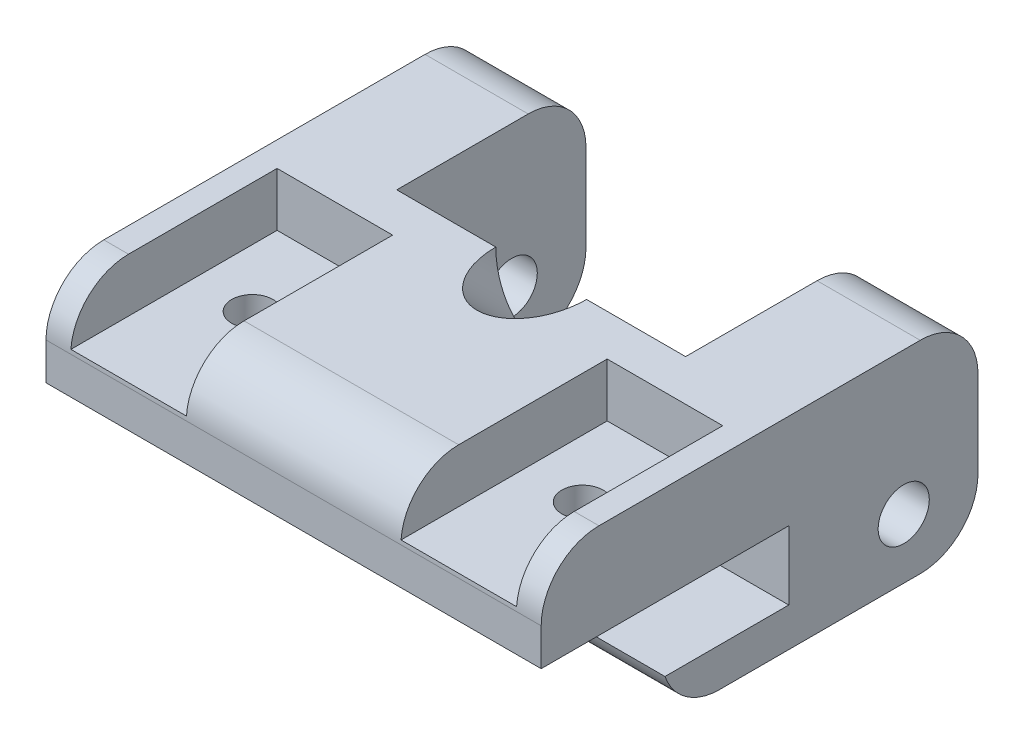
SolidWorks part; units mm, degrees
ref_plane "Alzado" through (0, 0, 0) normal (0, 0, 1) x (1, 0, 0)
ref_plane "Planta" through (0, 0, 0) normal (0, 1, 0) x (1, 0, 0)
ref_plane "Vista lateral" through (0, 0, 0) normal (1, 0, 0) x (0, 0, -1)
sketch "Croquis1" plane through (0, 0, 0) normal (0, 1, 0) x (1, 0, 0)
  line L0 (30, 0) -> (30, 30) construction
  line L1 (0, 0) -> (60, 0)
  line L2 (0, 0) -> (0, 30)
  line L3 (12.5, 30) -> (47.5, 30)
  line L4 (60, 0) -> (60, 30)
  line L5 (0, 15) -> (10, 15) construction
  line L6 (10, 15) -> (50, 15) construction
  line L7 (50, 15) -> (60, 15) construction
  line L8 (12.5, 52.93) -> (47.5, 52.93) construction
  line L10 (0, 30) -> (0, 52.93)
  line L11 (0, 52.93) -> (12.5, 52.93)
  line L12 (12.5, 30) -> (12.5, 52.93)
  line L14 (60, 30) -> (60, 52.93)
  line L15 (60, 52.93) -> (47.5, 52.93)
  line L16 (47.5, 30) -> (47.5, 52.93)
  line L17 (47.5, 30) -> (60, 30) construction
  circle A0 centre (10, 15) radius 2.5
  circle A1 centre (50, 15) radius 2.5
  point P9 (30, 15)
  dimension "D4" = 5
  dimension "D1" = 60
  dimension "D2" = 30
  dimension "D3" = 40
  dimension "D5" = 35
  dimension "D6" = 22.93
extrude "Saliente-Extruir1" add sketch "Croquis1" along normal blind 5 and the other way blind 13
sketch "Croquis2" plane through (0, 5, 0) normal (0, 1, 0) x (1, 0, 0)
  line L0 (10, 15) -> (3, 15) construction
  line L2 (3, 0) -> (3, 25)
  line L3 (3, 25) -> (17, 25)
  line L4 (57, 0) -> (57, 25)
  line L5 (50, 15) -> (57, 15) construction
  line L6 (57, 0) -> (60, 0)
  line L7 (0, 0) -> (60, 0) construction
  line L8 (0, 52.93) -> (0, 0)
  line L9 (0, 0) -> (60, 0)
  line L10 (60, 0) -> (60, 52.93)
  line L11 (60, 52.93) -> (47.5, 52.93)
  line L12 (47.5, 52.93) -> (47.5, 30)
  line L13 (47.5, 30) -> (12.5, 30)
  line L14 (12.5, 30) -> (12.5, 52.93)
  line L15 (12.5, 52.93) -> (0, 52.93)
  line L16 (0, 52.93) -> (0, 0)
  line L17 (0, 0) -> (3, 0)
  line L18 (60, 0) -> (60, 52.93)
  line L19 (60, 52.93) -> (47.5, 52.93)
  line L20 (47.5, 52.93) -> (47.5, 30)
  line L21 (47.5, 30) -> (12.5, 30)
  line L22 (12.5, 30) -> (12.5, 52.93)
  line L23 (12.5, 52.93) -> (0, 52.93)
  line L24 (17, 10.0834) -> (43, 10.0834) construction
  line L26 (17, 25) -> (17, 0)
  line L27 (17, 0) -> (43, 0)
  line L28 (43, 25) -> (43, 0)
  line L29 (30, 24.621) -> (30, 10.0834) construction
  line L30 (43, 25) -> (57, 25)
  line L31 (17, 25) -> (43, 25) construction
  line L32 (30, 30) -> (30, 24.621) construction
  line L33 (10, 15) -> (17, 15) construction
  dimension "D2" = 7
  dimension "D3" = 25
  dimension "D1" = 0
extrude "Saliente-Extruir2" add sketch "Croquis2" along normal blind 6.5 and the other way blind 10
sketch "Croquis4" plane through (0, 0, 0) normal (-1, 0, 0) x (0, 0, 1)
  line L0 (-52.93, -5.75) -> (-30, -5.75) construction
  line L1 (-52.93, -13) -> (0, -13) construction
  line L2 (-30, 11.5) -> (-30, -13) construction
  line L3 (-52.93, -13) -> (-52.93, 11.5) construction
  line L4 (-52.93, 11.5) -> (-52.93, -13) construction
  line L5 (-30, -13) -> (0, -13)
  line L6 (-30, -13) -> (-30, 0)
  line L7 (-30, 0) -> (0, 0)
  line L8 (0, -13) -> (0, 0)
  circle A0 centre (-43.93, -5.75) radius 3.1
  point P14 (0, 0)
  point P16 (-52.93, -0.75)
  point P17 (-43.93, -2.851)
  point P18 (0, 0)
  point P21 (0, 0)
  dimension "D1" = 6.2
  dimension "D2" = 9
  dimension "D3" = 5
extrude "Cortar-Extruir2" cut sketch "Croquis4" against normal up to surface (60 mm away) up to face at (60, -0.75, -26.465)
ref_plane "Plano1" through (0, -9.25, -9.25) normal (0, -0.7071, -0.7071) x (-1, 0, 0)
sketch "Croquis5" plane through (0, -9.25, -9.25) normal (0, -0.7071, -0.7071) x (-1, 0, 0)
  line L0 (-47.5, 29.3449) -> (-12.5, 29.3449) construction
  circle A0 centre (-30, 29.3449) radius 5.5
  dimension "D1" = 11
extrude "Cortar-Extruir3" cut sketch "Croquis5" against normal blind 10 and the other way blind 10
sketch "Croquis6" plane through (0, 0, 0) normal (-1, 0, 0) x (0, 0, 1)
  line L1 (-30, -13) -> (-15, -13)
  line L2 (-30, -13) -> (-30, -8.3158)
  line L3 (-30, -8.3158) -> (-15, -8.3158)
  line L4 (-15, -13) -> (-15, -8.3158)
  dimension "D1" = 4.6842
  dimension "D2" = 15
extrude "Saliente-Extruir3" add sketch "Croquis6" against normal up to surface (60 mm away) up to face at (60, -5.75, -47.03)
fillet "Redondeo1" radius 7 6 edges at (30, -13, -15) (53.75, -13, -52.93) (6.25, -13, -52.93) (6.25, 11.5, -52.93) (53.75, 11.5, -52.93) (58.5, 11.5, 0)
